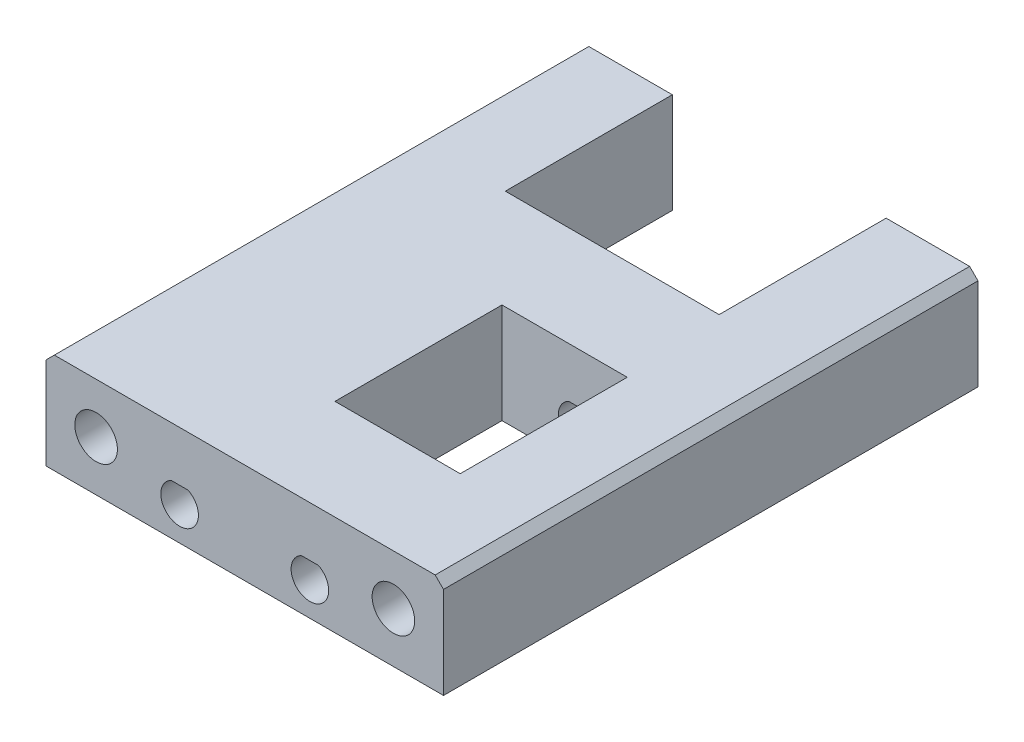
SolidWorks part; units mm, degrees
ref_plane "Front Plane" through (0, 0, 0) normal (0, 0, 1) x (1, 0, 0)
ref_plane "Top Plane" through (0, 0, 0) normal (0, 1, 0) x (1, 0, 0)
ref_plane "Right Plane" through (0, 0, 0) normal (1, 0, 0) x (0, 0, -1)
sketch "Sketch1" plane through (0, 0, 0) normal (0, 0, 1) x (1, 0, 0)
  line L0 (0, 0) -> (47.6, 0)
  line L1 (47.6, 0) -> (47.6, 6)
  line L2 (47.6, 6) -> (44.15, 6)
  line L3 (0, 6) -> (0, 0)
  line L4 (3.45, 6) -> (0, 6)
  line L5 (39.05, 6) -> (8.55, 6)
  arc A0 (3.45, 6) -> (8.55, 6) centre (6, 6) ccw
  arc A1 (39.05, 6) -> (44.15, 6) centre (41.6, 6) ccw
  dimension "D3" = 5.1
  dimension "D4" = 5.1
  dimension "D5" = 6
  dimension "D6" = 6
  dimension "D1" = 47.6
  dimension "D2" = 6
extrude "Boss-Extrude1" add sketch "Sketch1" along normal blind 44
sketch "Sketch2" plane through (0, 0, 44) normal (0, 0, 1) x (1, 0, 0)
  line L0 (0, 4) -> (47.6, 4) construction
  line L3 (0, 0) -> (47.6, 0) construction
  line L4 (0, 6) -> (0, 0) construction
  line L5 (47.6, 0) -> (47.6, 6) construction
  circle A0 centre (16, 4) radius 2.25
  circle A1 centre (31.6, 4) radius 2.25
  arc A2 (3.45, 6) -> (8.55, 6) centre (6, 6) ccw construction
  arc A3 (39.05, 6) -> (44.15, 6) centre (41.6, 6) ccw construction
  dimension "D1" = 4.5
  dimension "D2" = 4.5
  dimension "D3" = 10
  dimension "D4" = 10
  dimension "D5" = 4
extrude "Cut-Extrude1" cut sketch "Sketch2" against normal through all
sketch "Sketch4" plane through (0, 0, 0) normal (0, 0, -1) x (-1, 0, 0)
  line L0 (-11, 6) -> (-11, 0)
  line L1 (-39.05, 6) -> (-32.6308, 6) construction
  line L2 (0, 0) -> (-47.6, 0) construction
  line L3 (-11, 0) -> (0, 0)
  line L4 (0, 0) -> (0, 6)
  line L5 (0, 6) -> (-3.45, 6)
  line L6 (-11, 6) -> (-8.55, 6)
  line L7 (-36.6, 6) -> (-36.6, 0)
  line L8 (-36.6, 0) -> (-47.6, 0)
  line L9 (-47.6, 0) -> (-47.6, 6)
  line L10 (-47.6, 6) -> (-44.15, 6)
  line L11 (-39.05, 6) -> (-36.6, 6)
  arc A0 (-8.55, 6) -> (-3.45, 6) centre (-6, 6) ccw
  arc A1 (-44.15, 6) -> (-39.05, 6) centre (-41.6, 6) ccw
  arc A2 (-44.15, 6) -> (-39.05, 6) centre (-41.6, 6) ccw construction
  dimension "D1" = 11
  dimension "D2" = 2.55
  dimension "D3" = 11
extrude "Boss-Extrude2" add sketch "Sketch4" along normal blind 20
sketch "Sketch5" plane through (0, 0, 44) normal (0, 0, 1) x (1, 0, 0)
  line L0 (0, 6) -> (0, 12)
  line L1 (0, 12) -> (47.6, 12)
  line L2 (47.6, 12) -> (47.6, 6)
  line L3 (0, 6) -> (3.45, 6)
  line L4 (47.6, 6) -> (44.15, 6)
  line L5 (8.55, 6) -> (39.05, 6)
  arc A0 (8.55, 6) -> (3.45, 6) centre (6, 6) ccw
  arc A1 (44.15, 6) -> (39.05, 6) centre (41.6, 6) ccw
  dimension "D1" = 6
extrude "Boss-Extrude3" add sketch "Sketch5" against normal up to surface (64 mm away) up to face at (5.6667, 3.575, -20)
sketch "Sketch6" plane through (0, 6, 0) normal (0, -1, 0) x (1, 0, 0)
  line L0 (47.6, -20) -> (36.6, -20) construction
  line L1 (11, 0) -> (36.6, 0)
  line L2 (11, 0) -> (11, -20)
  line L3 (11, -20) -> (36.6, -20)
  line L4 (36.6, 0) -> (36.6, -20)
  line L5 (36.6, -20) -> (36.6, 0) construction
extrude "Cut-Extrude2" cut sketch "Sketch6" against normal through all
chamfer "Chamfer1" distance 10 angle 5 2 edges at (39.05, 6, -20) (3.45, 6, -20) first distance on face at (39.05, 6, -20) first distance on face at (3.45, 6, -20)
chamfer "Chamfer2" distance 1 angle 45 2 edges at (0, 12, 12) (47.6, 12, 12)
sketch "Sketch7" plane through (0, 0, 0) normal (0, -1, 0) x (1, 0, 0)
  line L0 (11, 0) -> (36.6, 0) construction
  line L1 (37.6, 12) -> (22.6, 12)
  line L2 (37.6, 12) -> (37.6, 32)
  line L3 (37.6, 32) -> (22.6, 32)
  line L4 (22.6, 12) -> (22.6, 32)
  line L5 (47.6, 44) -> (47.6, -20) construction
  dimension "D1" = 12
  dimension "D2" = 10
  dimension "D3" = 20
  dimension "D4" = 15
extrude "Cut-Extrude3" cut sketch "Sketch7" against normal through all
